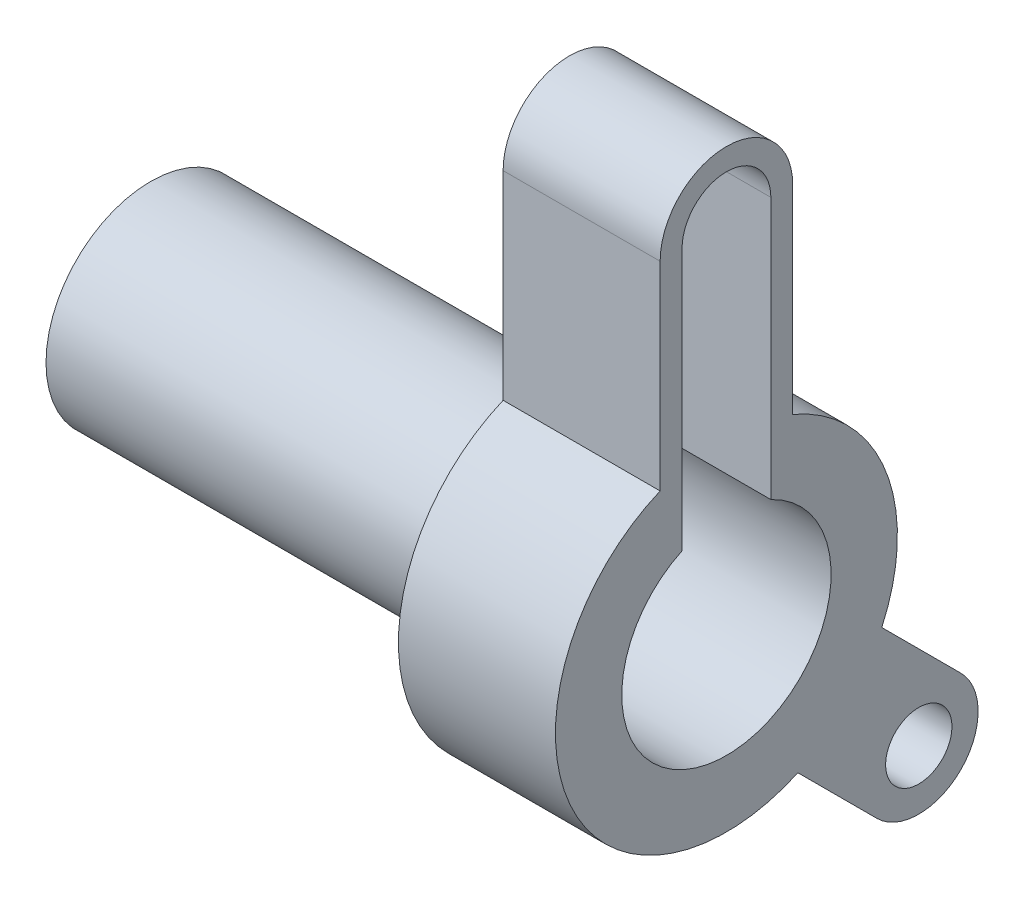
SolidWorks part; units mm, degrees
ref_plane "Спереди" through (0, 0, 0) normal (0, 0, 1) x (1, 0, 0)
ref_plane "Сверху" through (0, 0, 0) normal (0, 1, 0) x (1, 0, 0)
ref_plane "Справа" through (0, 0, 0) normal (1, 0, 0) x (0, 0, -1)
sketch "Эскиз1" plane through (0, 0, 0) normal (0, 0, 1) x (1, 0, 0)
  line L0 (120, -30) -> (165, -30)
  line L1 (0, 0) -> (120, 0)
  line L2 (0, 0) -> (0, -30)
  line L3 (0, -30) -> (120, -30)
  line L4 (120, 0) -> (120, -30)
  line L5 (120, 0) -> (165, 0)
  line L6 (120, 0) -> (120, -49)
  line L7 (120, -49) -> (165, -49)
  line L8 (165, 0) -> (165, -49)
  line L9 (120, -10) -> (0, -10)
  dimension "D1" = 165
  dimension "D2" = 120
  dimension "D3" = 49
  dimension "D4" = 30
  dimension "D5" = 10
revolve "Повернуть1" add sketch "Эскиз1" angle 360 about L1 region at (60, -20, 0) region at (142.5, -39.5, 0)
sketch "Эскиз2" plane through (165, 0, 0) normal (1, 0, 0) x (0, 0, -1)
  line L0 (0, -49) -> (0, 49) construction
  line L1 (0, 49) -> (0, 106) construction
  line L2 (-19, 45.1664) -> (-19, 102.1664)
  line L3 (19, 102.1664) -> (19, 45.1664)
  line L4 (12.7275, 27.1664) -> (12.7275, 102.1664)
  line L5 (-12.7275, 102.1664) -> (-12.7275, 27.1664)
  line L6 (0, 0) -> (85.6938, -85.6938) construction
  line L7 (44.517, -20.4753) -> (67.1444, -43.1028)
  line L8 (43.1028, -67.1444) -> (20.4753, -44.517)
  circle A0 centre (0, 0) radius 49 construction
  arc A1 (-19, 102.1664) -> (19, 102.1664) centre (0, 102.1664) cw
  circle A2 centre (0, 0) radius 30 construction
  arc A3 (12.7275, 102.1664) -> (-12.7275, 102.1664) centre (0, 102.1664) ccw
  arc A4 (19, 45.1664) -> (-19, 45.1664) centre (0, 0) ccw
  arc A5 (12.7275, 27.1664) -> (-12.7275, 27.1664) centre (0, 0) ccw
  arc A6 (67.1444, -43.1028) -> (43.1028, -67.1444) centre (55.1236, -55.1236) cw
  arc A7 (20.4753, -44.517) -> (44.517, -20.4753) centre (0, 0) ccw
  arc A8 (19, 45.1664) -> (-19, 45.1664) centre (0, 0) ccw
  circle A9 centre (55.1236, -55.1236) radius 9.5
  point P26 (0, 0)
  point P27 (0, 0)
  point P28 (46.4675, -71.2163)
  point P29 (46.4675, -71.2163)
  point P30 (0, 0)
  point P31 (0, 0)
  circle M16 centre (0, 0) radius 49
  circle M17 centre (0, 0) radius 30
  dimension "D1" = 57
  dimension "D5" = 32
  dimension "D6" = 19
  dimension "D7" = 17
  dimension "D2" = 75
  dimension "D3" = 38
  dimension "D4" = 45
  dimension "D8" = 34
extrude "Бобышка-Вытянуть1" add sketch "Эскиз2" against normal up to surface (45 mm away) contours A3 L4 L3 A1 L2 L5 M16 | A6 L7 L8 A9 M16 region at (165, 73.6664, 18.1503) region at (165, -47.9896, -47.9896) up to face at (120, 0, 49)
extrude "Вырез-Вытянуть1" cut sketch "Эскиз2<4>" against normal through all contours L5 L4 M16 M17 region at (165, 38.747, 0)
sketch "Эскиз2<4>" plane through (165, 0, 0) normal (1, 0, 0) x (0, 0, -1) same geometry as "Эскиз2"
